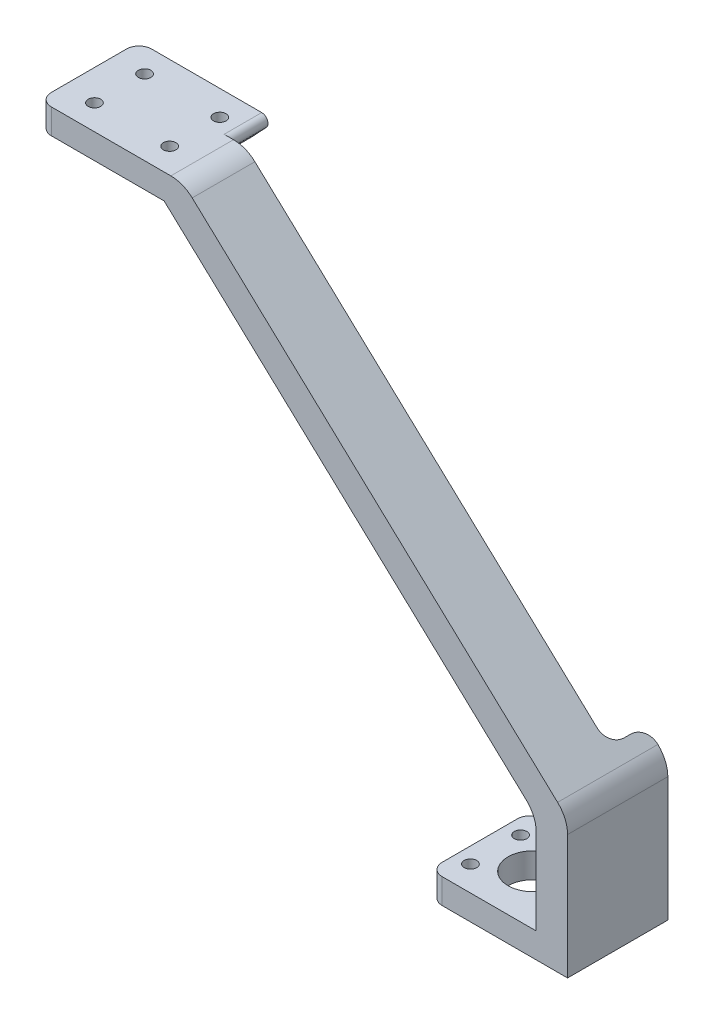
SolidWorks part; units mm, degrees
material "聚脂树脂"
ref_plane "前视基准面" through (0, 0, 0) normal (0, 0, 1) x (1, 0, 0)
ref_plane "上视基准面" through (0, 0, 0) normal (0, 1, 0) x (1, 0, 0)
ref_plane "右视基准面" through (0, 0, 0) normal (1, 0, 0) x (0, 0, -1)
other "Configuration Table"
sketch "草图1" plane through (0, 0, 0) normal (0, 1, 0) x (1, 0, 0)
  line L0 (0, 0) -> (0, 15.4433) construction
  line L1 (-8.5, -8) -> (8.5, -8)
  line L2 (-8.5, -8) -> (-8.5, 8)
  line L3 (-8.5, 8) -> (8.5, 8)
  line L4 (8.5, -8) -> (8.5, 8)
  line L5 (-8.5, -8) -> (8.5, 8) construction
  line L6 (-8.5, 8) -> (8.5, -8) construction
  line L7 (0, 0) -> (21.5354, 0) construction
  circle A0 centre (6, 4) radius 1
  circle A1 centre (-6, 4) radius 1
  circle A2 centre (6, -4) radius 1
  circle A3 centre (-6, -4) radius 1
  circle A4 centre (0, 0) radius 4
  point P0 (0, 0)
  dimension "D3" = 2
  dimension "D4" = 12
  dimension "D5" = 8
  dimension "D6" = 8
  dimension "D1" = 17
  dimension "D2" = 16
extrude "凸台-拉伸1" add sketch "草图1" along normal blind 4
sketch "草图2" plane through (0, 0, 8) normal (0, 0, 1) x (1, 0, 0)
  line L0 (8.5, 4.8259) -> (8.5, 0)
  line L1 (8.5, 4) -> (8.5, 0) construction
  line L2 (-8.5, 0) -> (8.5, 0) construction
  line L3 (8.5, 0) -> (13.5, 0)
  line L4 (13.5, 0) -> (13.5, 22)
  line L6 (-50.6912, 79.2) -> (-70.8814, 79.2)
  line L7 (-70.8814, 79.2) -> (-70.8814, 75.2)
  line L8 (-67, 75.2) -> (-70, 75.2) construction
  line L9 (-70.8814, 75.2) -> (-51, 75.2)
  line L11 (8.5, 19.8259) -> (8.5, 4.8259)
  line L12 (13.5, 22) -> (-47.8395, 79.2)
  line L13 (-47.8395, 79.2) -> (-50.6912, 79.2)
  line L14 (-51, 75.2) -> (-50.8814, 75.2)
  line L15 (-50.8814, 75.2) -> (8.5, 19.8259)
  dimension "D1" = 5
  dimension "D2" = 5
  dimension "D3" = 4
  dimension "D4" = 20
  dimension "D5" = 133
  dimension "D6" = 15
  dimension "D7" = 22
extrude "凸台-拉伸2" add sketch "草图2" against normal blind 16
sketch "草图4" plane through (0, 75.2, 0) normal (0, -1, 0) x (1, 0, 0)
  circle A0 centre (-54, 4) radius 1
  circle A1 centre (-54, -4) radius 1
  circle A2 centre (-66, -4) radius 1
  circle A3 centre (-66, 4) radius 1
  dimension "D1" = 2
  dimension "D2" = 2
  dimension "D3" = 2
  dimension "D4" = 2
extrude "切除-拉伸1" cut sketch "草图4" against normal blind 16
fillet "圆角1" radius 2 4 edges at (-8.5, 2, -8) (-8.5, 2, 8) (-70.8814, 77.2, -8) (-70.8814, 77.2, 8)
fillet "圆角2" radius 5 3 edges at (-47.8395, 79.2, 0) (13.5, 22, 0) (8.5, 19.8259, 0)
sketch "草图7" plane through (17.2523, 18.5009, 0) normal (0.682, 0.7314, 0) x (0, 0, -1)
  line L0 (2, 89.8537) -> (8, 89.8537)
  line L2 (8, 89.8537) -> (8, 9.8537)
  line L3 (8, 9.8537) -> (2, 9.8537)
  line L4 (2, 9.8537) -> (2, 89.8537)
  line L5 (6, 105.8537) -> (-6, 105.8537) construction
  line L6 (8, 7.3048) -> (8, 87.0323) construction
  dimension "D1" = 6
  dimension "D2" = 16
  dimension "D3" = 80
extrude "切除-拉伸2" cut sketch "草图7" against normal blind 10
fillet "圆角3" radius 1 1 edges at (-49.0572, 79.1431, -5)
fillet "圆角4" radius 2.5 3 edges at (6.7729, 21.4365, -8) (8.3408, 23.3927, -2) (8.3408, 23.3927, -8)
